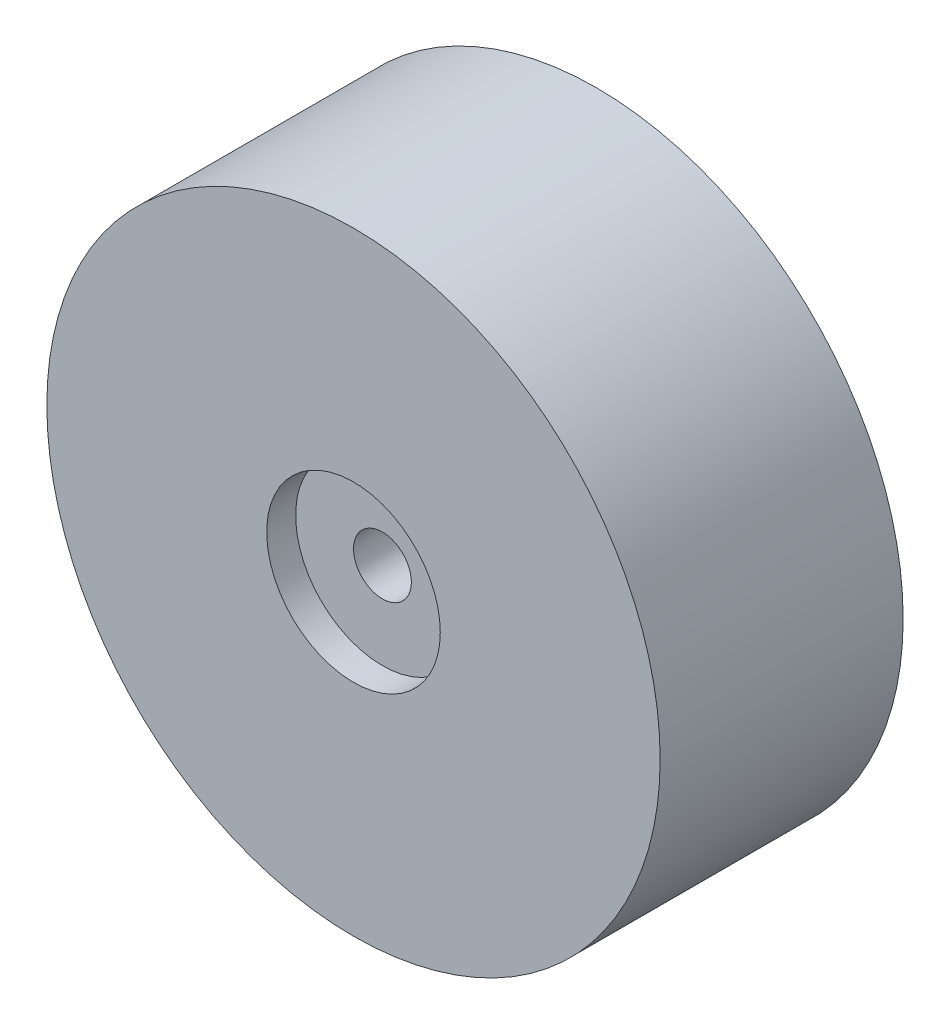
SolidWorks part; units mm, degrees
ref_plane "Front Plane" through (0, 0, 0) normal (0, 0, 1) x (1, 0, 0)
ref_plane "Top Plane" through (0, 0, 0) normal (0, 1, 0) x (1, 0, 0)
ref_plane "Right Plane" through (0, 0, 0) normal (1, 0, 0) x (0, 0, -1)
sketch "Sketch1" plane through (0, 0, 0) normal (0, 0, 1) x (1, 0, 0)
  circle A0 centre (0, 0) radius 26.5
  circle A1 centre (0, 0) radius 7.5
  dimension "D1" = 53
  dimension "D2" = 15
extrude "Boss-Extrude1" add sketch "Sketch1" along normal blind 10.5 and the other way blind 10.5
sketch "Sketch3" plane through (0, 0, 0) normal (0, 0, 1) x (1, 0, 0)
  circle A0 centre (0, 0) radius 7.5
  circle A1 centre (0, 0) radius 2.5
  dimension "D1" = 5
extrude "Boss-Extrude2" add sketch "Sketch3" along normal blind 8 and the other way blind 8
